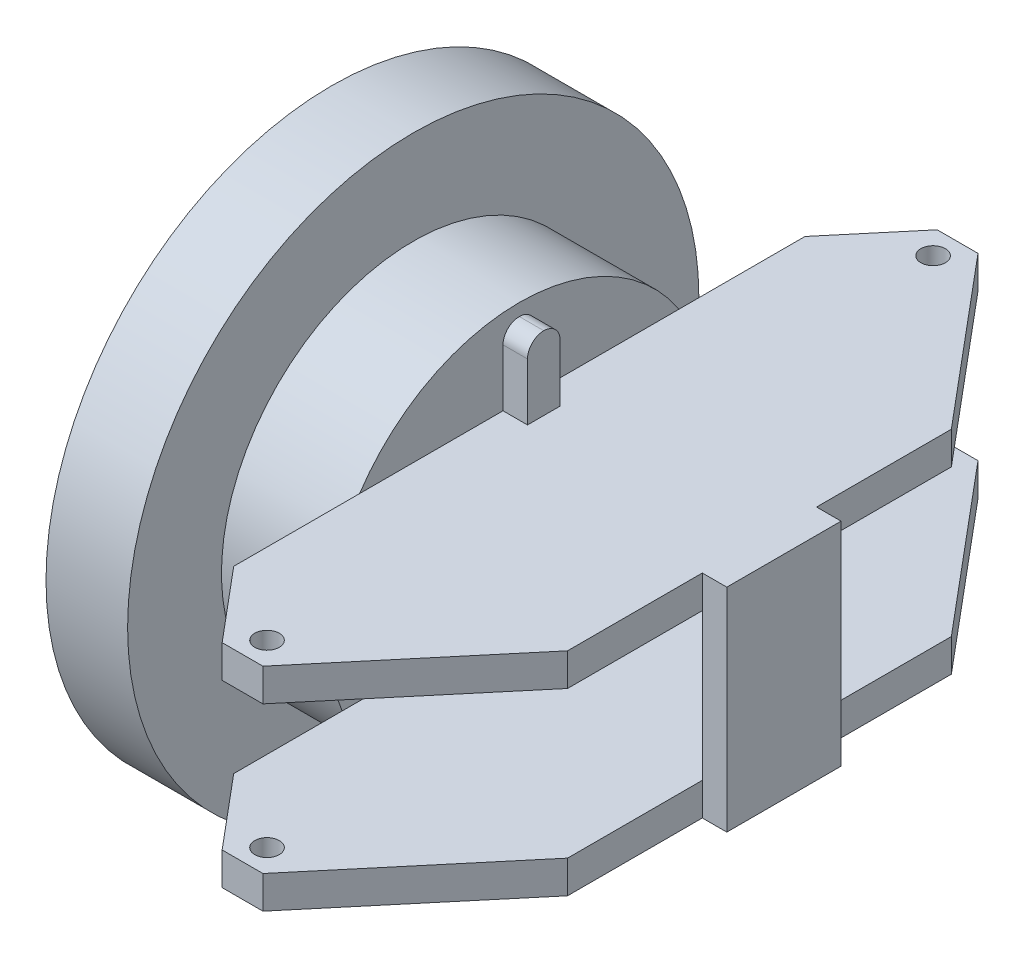
SolidWorks part; units mm, degrees
ref_plane "Front Plane" through (0, 0, 0) normal (0, 0, 1) x (1, 0, 0)
ref_plane "Top Plane" through (0, 0, 0) normal (0, 1, 0) x (1, 0, 0)
ref_plane "Right Plane" through (0, 0, 0) normal (1, 0, 0) x (0, 0, -1)
sketch "Sketch1" plane through (0, 0, 0) normal (1, 0, 0) x (0, 0, -1)
  circle A0 centre (0, 0) radius 35
  dimension "D1" = 70
extrude "Boss-Extrude1" add sketch "Sketch1" along normal blind 10
sketch "Sketch2" plane through (10, 0, 0) normal (1, 0, 0) x (0, 0, -1)
  circle A0 centre (0, 0) radius 23.5
  dimension "D1" = 47
extrude "Boss-Extrude2" add sketch "Sketch2" along normal blind 13
ref_plane "Plane1" through (0, 13, 0) normal (0, 1, 0) x (1, 0, 0)
sketch "Sketch3" plane through (0, 13, 0) normal (0, 1, 0) x (1, 0, 0)
  line L0 (23, 35) -> (23, -35)
  line L2 (23, -35) -> (30.3921, -43.8095)
  line L3 (30.3921, -43.8095) -> (35.3921, -43.8095)
  line L4 (35.3921, -43.8095) -> (52.4218, -23.5143)
  line L6 (52.4218, -23.5143) -> (52.4218, 0)
  line L8 (23, 35) -> (47.7049, 35) construction
  line L9 (52.4218, 23.5143) -> (52.4218, 0)
  line L10 (35.3921, 43.8095) -> (52.4218, 23.5143)
  line L11 (30.3921, 43.8095) -> (35.3921, 43.8095)
  line L12 (23, 35) -> (30.3921, 43.8095)
  line L13 (23, -23.5314) -> (56.1734, -23.5314) construction
  line L14 (23, 23.421) -> (61.7469, 23.421) construction
  dimension "D2" = 11.5
  dimension "D3" = 40
  dimension "D4" = 5
  dimension "D5" = 50
extrude "Boss-Extrude3" add sketch "Sketch3" against normal blind 4
sketch "Sketch5" plane through (0, 13, 0) normal (0, 1, 0) x (1, 0, 0)
  line L0 (30.3921, -43.8095) -> (35.3921, -43.8095) construction
  circle A0 centre (32.8921, -40.8095) radius 1.5
  dimension "D1" = 3
  dimension "D2" = 3
extrude "Cut-Extrude1" cut sketch "Sketch5" against normal blind 4
mirror "Mirror2" about plane through (0, 0, 0) normal (0, 0, 1) of "Cut-Extrude1"
mirror "Mirror3" about plane through (0, 0, 0) normal (0, 1, 0) of "Cut-Extrude1", "Boss-Extrude3", "Mirror2"
sketch "Sketch7" plane through (23, 0, 0) normal (1, 0, 0) x (0, 0, -1)
  line L0 (0, 13) -> (0, 22) construction
  line L1 (35, 13) -> (-35, 13) construction
  line L2 (0, 22) -> (-2, 22)
  line L3 (-2, 22) -> (-2, 13)
  line L4 (0, 22) -> (2, 22)
  line L5 (2, 22) -> (2, 13)
  line L6 (-2, 13) -> (2, 13)
  dimension "D1" = 9
  dimension "D2" = 2
  dimension "D3" = 2
extrude "Boss-Extrude4" add sketch "Sketch7" along normal blind 3
fillet "Fillet1" radius 2 2 edges at (24.5, 22, 2) (24.5, 22, -2)
mirror "Mirror5" about plane through (0, 0, 0) normal (0, 1, 0) of "Fillet1", "Boss-Extrude4"
sketch "Sketch8" plane through (52.4218, 0, 0) normal (1, 0, 0) x (0, 0, -1)
  line L1 (-7, -13) -> (7, -13)
  line L2 (-7, -13) -> (-7, 13)
  line L3 (-7, 13) -> (7, 13)
  line L4 (7, -13) -> (7, 13)
  line L5 (-7, -13) -> (7, 13) construction
  line L6 (-7, 13) -> (7, -13) construction
  point P0 (0, 0)
  dimension "D1" = 26
  dimension "D2" = 14
extrude "Boss-Extrude5" add sketch "Sketch8" along normal blind 3
sketch "Sketch9" plane through (0, 0, 0) normal (-1, 0, 0) x (0, 0, 1)
  circle A0 centre (0, 0) radius 10
  dimension "D1" = 20
extrude "Cut-Extrude2" cut sketch "Sketch9" against normal blind 10 contours A0
